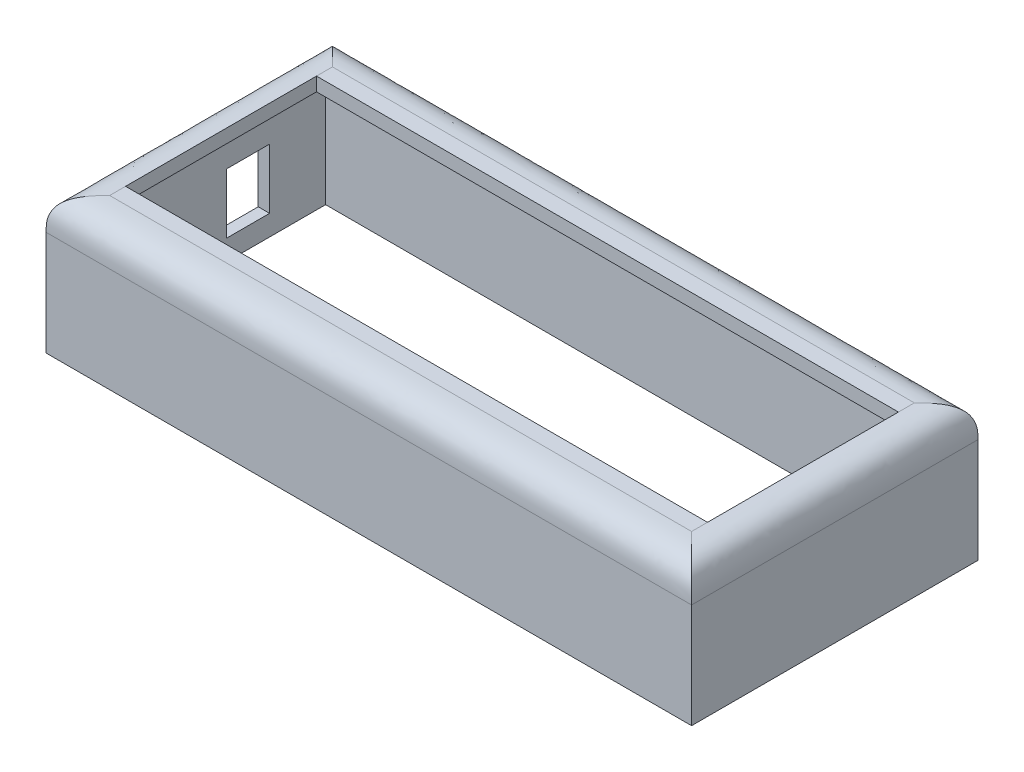
SolidWorks part; units mm, degrees
ref_plane "Front Plane" through (0, 0, 0) normal (0, 0, 1) x (1, 0, 0)
ref_plane "Top Plane" through (0, 0, 0) normal (0, 1, 0) x (1, 0, 0)
ref_plane "Right Plane" through (0, 0, 0) normal (1, 0, 0) x (0, 0, -1)
sketch "Sketch1" plane through (0, 0, 0) normal (0, 1, 0) x (1, 0, 0)
  line L1 (-71, 31.5) -> (71, 31.5)
  line L2 (-71, 31.5) -> (-71, -31.5)
  line L3 (-71, -31.5) -> (71, -31.5)
  line L4 (71, 31.5) -> (71, -31.5)
  line L5 (-71, 31.5) -> (71, -31.5) construction
  line L6 (-71, -31.5) -> (71, 31.5) construction
  point P0 (0, 0)
  dimension "D1" = 142
  dimension "D2" = 63
extrude "Boss-Extrude2" add sketch "Sketch1" along normal blind 30
sketch "Sketch3" plane through (0, 0, 0) normal (0, -1, 0) x (1, 0, 0)
  line L1 (-64, 21) -> (64, 21)
  line L2 (-64, 21) -> (-64, -21)
  line L3 (-64, -21) -> (64, -21)
  line L4 (64, 21) -> (64, -21)
  line L5 (-64, 21) -> (64, -21) construction
  line L6 (-64, -21) -> (64, 21) construction
  point P0 (0, 0)
  dimension "D1" = 128
  dimension "D2" = 42
extrude "Cut-Extrude2" cut sketch "Sketch3" against normal blind 30
fillet "Fillet5" radius 7 4 edges at (-71, 30, 0) (0, 30, -31.5) (71, 30, 0) (0, 30, 31.5) curvature continuous yes
sketch "Sketch4" plane through (0, 0, 0) normal (0, -1, 0) x (1, 0, 0)
  line L1 (-68.5, 27.5) -> (68.5, 27.5)
  line L2 (-68.5, 27.5) -> (-68.5, -27.5)
  line L3 (-68.5, -27.5) -> (68.5, -27.5)
  line L4 (68.5, 27.5) -> (68.5, -27.5)
  line L5 (-68.5, 27.5) -> (68.5, -27.5) construction
  line L6 (-68.5, -27.5) -> (68.5, 27.5) construction
  point P0 (0, 0)
  dimension "D1" = 137
  dimension "D2" = 55
extrude "Cut-Extrude4" cut sketch "Sketch4" against normal blind 27
ref_axis "Axis1" through (-64.8677, 10.6467, -10.45) along (-1, 0, 0)
sketch "Sketch7" plane through (-71, 0, 0) normal (-1, 0, 0) x (0, 0, 1)
  line L1 (-15.177, 4.5129) -> (-5.6535, 4.5129)
  line L2 (-15.177, 4.5129) -> (-15.177, 17.7034)
  line L3 (-15.177, 17.7034) -> (-5.6535, 17.7034)
  line L4 (-5.6535, 4.5129) -> (-5.6535, 17.7034)
  line L5 (-15.177, 4.5129) -> (-5.6535, 17.7034) construction
  line L6 (-15.177, 17.7034) -> (-5.6535, 4.5129) construction
  point P0 (-10.4153, 11.1081)
extrude "Cut-Extrude5" cut sketch "Sketch7" against normal blind 10
